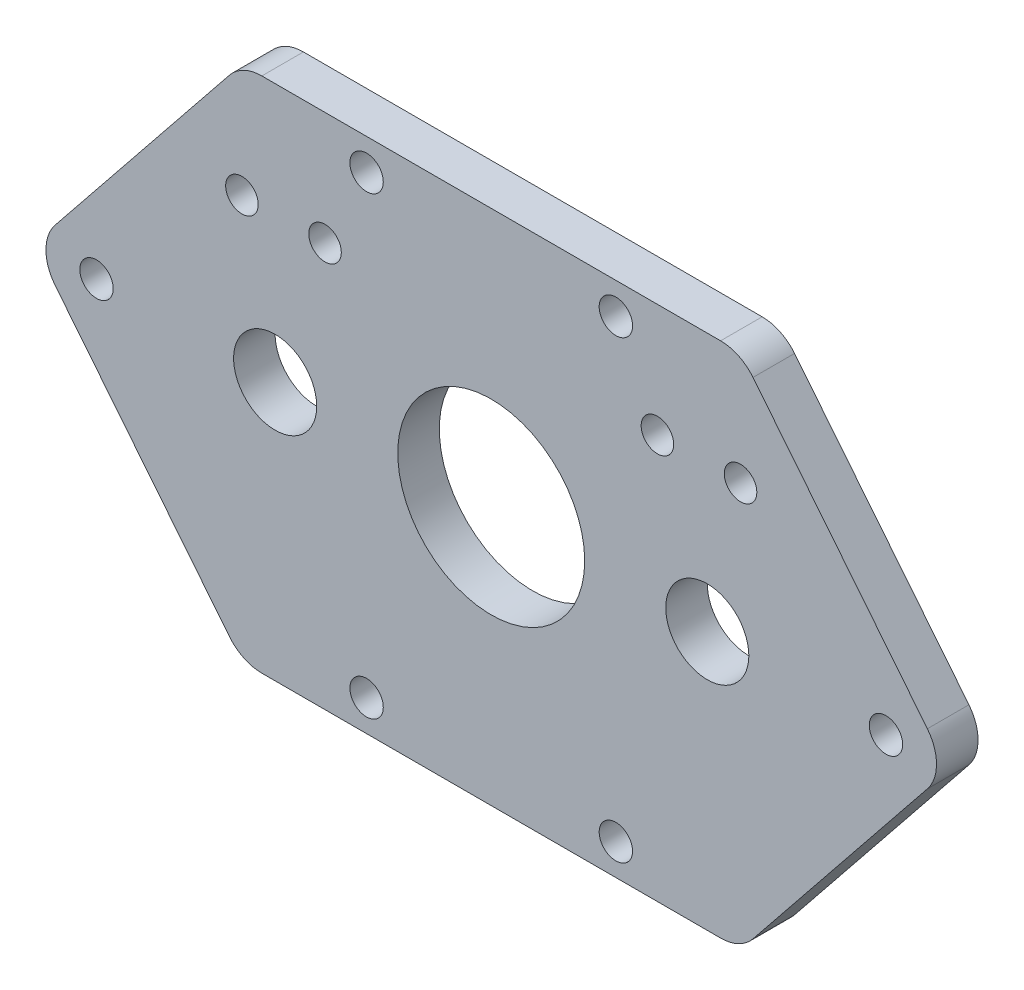
SolidWorks part; units mm, degrees
material "6061-T6 (SS)"
ref_plane "Front Plane" through (0, 0, 0) normal (0, 0, 1) x (1, 0, 0)
ref_plane "Top Plane" through (0, 0, 0) normal (0, 1, 0) x (1, 0, 0)
ref_plane "Right Plane" through (0, 0, 0) normal (1, 0, 0) x (0, 0, -1)
sketch "Sketch5" plane through (0, 0, 0) normal (0, 0, 1) x (1, 0, 0)
  line L0 (-19.7318, -15.9943) -> (19.7318, 15.9943) construction
  line L1 (0, 0) -> (25.4, 0) construction
  line L2 (-19.05, 34.7624) -> (19.05, 34.7624) construction
  line L3 (-38.1, -39.5249) -> (38.1, -39.5249)
  line L5 (-38.1, 39.5249) -> (38.1, 39.5249)
  line L7 (-38.1, -39.5249) -> (38.1, 39.5249) construction
  line L8 (-38.1, 39.5249) -> (38.1, -39.5249) construction
  line L9 (-39.37, 0) -> (39.37, 0) construction
  line L10 (-19.05, -34.7624) -> (19.05, -34.7624) construction
  line L11 (0, 39.5249) -> (0, -39.5249) construction
  line L12 (38.1, -39.5249) -> (-38.1, -39.5249)
  line L16 (-39.37, -12.7) -> (39.37, -12.7) construction
  line L17 (-39.37, -12.7) -> (-39.37, -10.4954) construction
  line L18 (-39.37, 12.7) -> (39.37, 12.7) construction
  line L19 (39.37, -12.7) -> (39.37, 0) construction
  line L20 (-39.37, -12.7) -> (39.37, 12.7) construction
  line L21 (-39.37, 12.7) -> (39.37, -12.7) construction
  line L22 (-38.1, 39.5249) -> (-69.85, 0)
  line L23 (-38.1, -39.5249) -> (-69.85, 0)
  line L24 (0, 39.5249) -> (0, -39.5249) construction
  line L25 (38.1, -39.5249) -> (69.85, 0)
  line L26 (38.1, 39.5249) -> (69.85, 0)
  line L28 (-39.37, 0) -> (-39.37, 12.7) construction
  line L29 (39.37, 2.9966) -> (39.37, 12.7) construction
  line L31 (69.85, 0) -> (38.1, -39.5249)
  line L33 (-38.1, 22.225) -> (-25.4, 22.225) construction
  line L38 (-31.75, 12.7) -> (-31.75, 28.575) construction
  line L39 (-59.6482, 12.7) -> (59.6482, 12.7) construction
  line L40 (-19.05, 12.7) -> (-44.45, 12.7) construction
  line L41 (-19.05, 12.7) -> (-19.05, 28.575) construction
  line L42 (-19.05, 28.575) -> (-44.45, 28.575) construction
  line L43 (-44.45, 12.7) -> (-44.45, 28.575) construction
  line L44 (-19.05, 15.875) -> (-44.45, 15.875) construction
  circle A0 centre (0, 0) radius 14.2875
  circle A1 centre (0, 0) radius 25.4 construction
  circle A6 centre (-19.05, 34.7624) radius 2.5527
  circle A7 centre (19.05, 34.7624) radius 2.5527
  circle A8 centre (19.05, -34.7624) radius 2.5527
  circle A9 centre (-19.05, -34.7624) radius 2.5527
  circle A18 centre (60.325, 0) radius 2.5527
  circle A19 centre (-60.325, 0) radius 2.5527
  circle A21 centre (-33.02, 0) radius 6.35
  circle A22 centre (33.02, 0) radius 6.35
  circle A25 centre (-38.1, 22.225) radius 2.4892
  circle A26 centre (-25.4, 22.225) radius 2.4892
  circle A29 centre (25.4, 22.225) radius 2.4892
  circle A30 centre (38.1, 22.225) radius 2.4892
  point P8 (0, 0)
  point P19 (0, 34.7624)
  point P37 (0, -25.4)
  point P49 (33.02, -39.5249)
  point P52 (-38.1, -45.7794)
  point P55 (39.37, 0)
  point P59 (-31.75, 22.225)
  point P64 (-63.5, 0)
  point P65 (0, 0)
  point P66 (0, 0)
  point P67 (0, 0)
  point P68 (-38.4056, 3.3643)
  point P69 (0, 0)
  point P70 (0, 0)
  point P71 (38.6185, 2.9966)
  point P72 (0, 0)
  point P73 (0, 0)
  point P74 (0, 0)
  point P75 (0, 0)
  point P76 (-39.37, -10.4954)
  point P77 (-38.1, 39.5249)
  point P78 (0, 0)
  dimension "D1" = 28.575
  dimension "D2" = 5.1054
  dimension "D3" = 50.8
  dimension "D5" = 19.05
  dimension "D6" = 5.1054
  dimension "D8" = 4.7625
  dimension "D11" = 12.7
  dimension "D12" = 25.4
  dimension "D13" = 60.325
  dimension "D14" = 60.325
  dimension "D10" = 2
  dimension "D16" = 33.02
  dimension "D17" = 12.7
  dimension "D18" = 4.9784
  dimension "D19" = 9.525
  dimension "D23" = 25.4
  dimension "D4" = 34.7624
  dimension "45" = 39.028
  dimension "D7" = 4.7625
  dimension "D9" = 25.4
  dimension "D15" = 69.85
  dimension "D20" = 3.175
  dimension "D21" = 12.7
  dimension "D22" = 15.875
  dimension "D24" = 76.2
extrude "Boss-Extrude1" add sketch "Sketch5" along normal blind 6.35 contours L3 | A21 L22 L23 A19 | A22 L5 A21 L3 A9 A0 A6 A7 A8 | L26 A22 L25 A18 region at (-52.7236, -18.7572, 0)
fillet "Fillet2" radius 6.35 6 edges at (38.1, -39.5249, 3.175) (-38.1, -39.5249, 3.175) (38.1, 39.5249, 3.175) (-38.1, 39.5249, 3.175) (69.85, 0, 3.175) (-69.85, 0, 3.175)
equation "\"NEO\"= 60mm"
